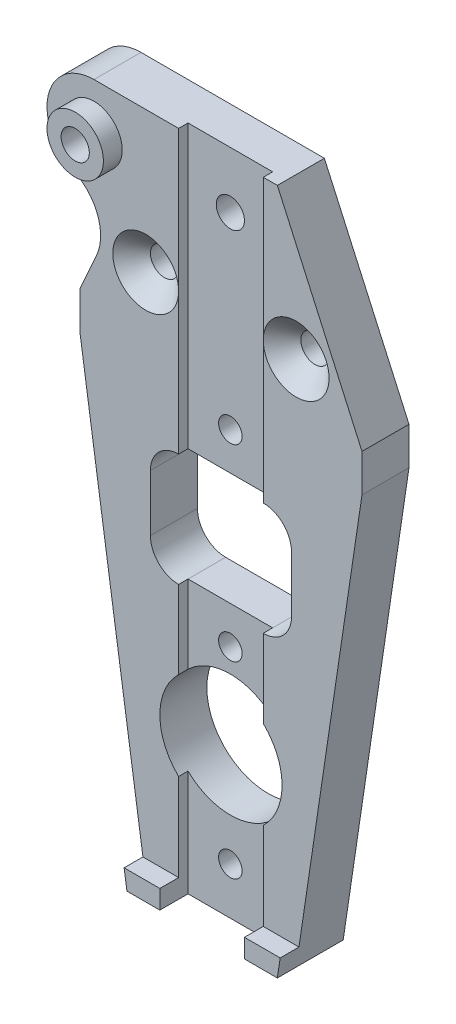
SolidWorks part; units mm, degrees
material "6061 合金"
ref_plane "前视基准面" through (0, 0, 0) normal (0, 0, 1) x (1, 0, 0)
ref_plane "上视基准面" through (0, 0, 0) normal (0, 1, 0) x (1, 0, 0)
ref_plane "右视基准面" through (0, 0, 0) normal (1, 0, 0) x (0, 0, -1)
sketch "草图1" plane through (0, 0, 0) normal (0, 0, 1) x (1, 0, 0)
  line L0 (0, 0) -> (0, 77.5694) construction
  line L1 (6, 55) -> (-6, 55)
  line L2 (-7.5, 13) -> (7.5, 13)
  line L3 (-7.5, 13) -> (-7.5, 25)
  line L4 (-7.5, 25) -> (7.5, 25)
  line L5 (7.5, 13) -> (7.5, 25)
  line L6 (-7.5, 13) -> (7.5, 25) construction
  line L7 (-7.5, 25) -> (7.5, 13) construction
  line L8 (-6, 55) -> (-15, 35)
  line L10 (-15, 35) -> (15, 35) construction
  line L11 (-4.5, 55) -> (-4.5, 39.2144) construction
  line L13 (6, 55) -> (15, 35)
  line L15 (-8, -16) -> (8, -16)
  line L16 (0, 0) -> (0, -39.4346) construction
  line L18 (-15, 35) -> (-15, 31)
  line L19 (-15, 31) -> (-8, -16)
  line L20 (15, 31) -> (8, -16)
  line L21 (15, 35) -> (15, 31)
  circle A0 centre (0, 0) radius 6.5
  circle A2 centre (0, 49) radius 1.5
  circle A3 centre (-8, 40) radius 1.5
  circle A4 centre (0, 29) radius 1.25 construction
  circle A5 centre (0, 9) radius 1.25 construction
  circle A6 centre (0, -11) radius 1.25 construction
  circle A7 centre (8, 40) radius 1.5
  point P4 (0, 19)
  point P28 (0, -16)
  point P33 (0, 55)
  dimension "D1" = 13
  dimension "D5" = 35
  dimension "D8" = 3
  dimension "D9" = 14
  dimension "D10" = 3
  dimension "D11" = 16
  dimension "D13" = 2.5
  dimension "D14" = 20
  dimension "D15" = 2.5
  dimension "D16" = 20
  dimension "D17" = 2.5
  dimension "D18" = 20
  dimension "D20" = 5
  dimension "D21" = 5
  dimension "D2" = 15
  dimension "D3" = 12
  dimension "D4" = 13
  dimension "D6" = 6
  dimension "D7" = 20
  dimension "D12" = 4.5
  dimension "D19" = 30
  dimension "D22" = 8
  dimension "D23" = 4
extrude "凸台-拉伸1" add sketch "草图1" along normal blind 5
hole_wizard "M3 螺纹孔1" positions "草图7" profile "草图8" tap size "M3" standard "GB" end condition through all
sketch "草图7" plane through (0, 0, 5) normal (0, 0, 1) x (1, 0, 0)
  point P0 (0, 29)
  point P3 (0, 9)
  point P6 (0, -11)
sketch "草图8" plane through (0, 29, 5) normal (1, 0, 0) x (0, -1, 0)
  line L0 (0, 0) -> (0, 5)
  line L1 (0, 5) -> (1.25, 5)
  line L2 (1.25, 5) -> (1.25, 0)
  line L5 (1.25, 0) -> (0, 0)
  line L11 (0, -6.35) -> (0, 107.95) construction
  dimension "通孔螺纹孔钻头直径" = 2.5
  dimension "通孔螺纹孔钻头深度" = 5
cosmetic thread "孔螺纹线1" parameters "D2"=3
cosmetic thread "孔螺纹线2" parameters "D2"=3
cosmetic thread "孔螺纹线3" parameters "D2"=3
sketch "草图2" plane through (0, 0, 5) normal (0, 0, 1) x (1, 0, 0)
  line L0 (0, -18.9795) -> (0, 64.8101) construction
  line L1 (4.5, -18.9795) -> (4.5, 64.8101)
  line L2 (-4.5, -18.9795) -> (-4.5, 64.8101)
  line L3 (-4.5, 64.8101) -> (4.5, 64.8101)
  line L4 (-4.5, -18.9795) -> (4.5, -18.9795)
  dimension "D1" = 4.5
  dimension "D2" = 4.5
extrude "切除-拉伸1" cut sketch "草图2" against normal blind 1
fillet "圆角1" radius 3 4 edges at (7.5, 13, 2.5) (-7.5, 13, 2.5) (-7.5, 25, 2.5) (7.5, 25, 2.5)
sketch "草图4" plane through (0, 0, 5) normal (0, 0, 1) x (1, 0, 0)
  line L0 (-8, -16) -> (-4.5, -16) construction
  line L1 (-15, 31) -> (-8, -16) construction
  line L2 (-8, -16) -> (-4.5, -16)
  line L3 (-8.2979, -14) -> (-8, -16)
  line L4 (0, 0) -> (0, -29.8573) construction
  line L5 (-4.5, -16) -> (-4.5, -14)
  line L6 (-4.5, -4.6904) -> (-4.5, -16) construction
  line L7 (-4.5, -14) -> (-8.2979, -14)
  line L8 (4.5, -14) -> (8.2979, -14)
  line L9 (4.5, -16) -> (4.5, -14)
  line L10 (8, -16) -> (4.5, -16)
  line L11 (8.2979, -14) -> (8, -16)
  dimension "D1" = 2
extrude "凸台-拉伸2" add sketch "草图4" along normal blind 2
chamfer "倒角1" distance 2 angle 45 2 edges at (6.5, 40, 5) (-6.5, 40, 5)
sketch "草图5" plane through (0, 0, 5) normal (0, 0, 1) x (1, 0, 0)
  line L0 (6, 55) -> (13.5, 55)
  line L1 (15, 35) -> (6, 55) construction
  line L2 (9.7258, 46.7205) -> (6, 55)
  circle A0 centre (13.5, 50) radius 1.5
  circle A1 centre (0, 49) radius 1.5 construction
  arc A2 (9.7258, 46.7205) -> (13.5, 55) centre (13.5, 50) ccw
  dimension "D1" = 3
  dimension "D2" = 13.5
  dimension "D3" = 5
extrude "凸台-拉伸4" add sketch "草图5" against normal up to surface (5 mm away) up to face at (1.25, 29, 0)
fillet "圆角2" radius 5 1 edges at (9.7258, 46.7205, 2.5)
sketch "草图6" plane through (0, 0, 5) normal (0, 0, 1) x (1, 0, 0)
  circle A2 centre (13.5, 50) radius 1.5
  circle A3 centre (13.5, 50) radius 1.5 construction
  circle A4 centre (13.5, 50) radius 3
  dimension "D1" = 6
extrude "凸台-拉伸5" add sketch "草图6" along normal blind 2
mirror "镜向1" about plane through (0, 0, 0) normal (1, 0, 0) of bodies 111
delete or keep bodies "实体-删除/保留 1" type delete bodies bodies 111
